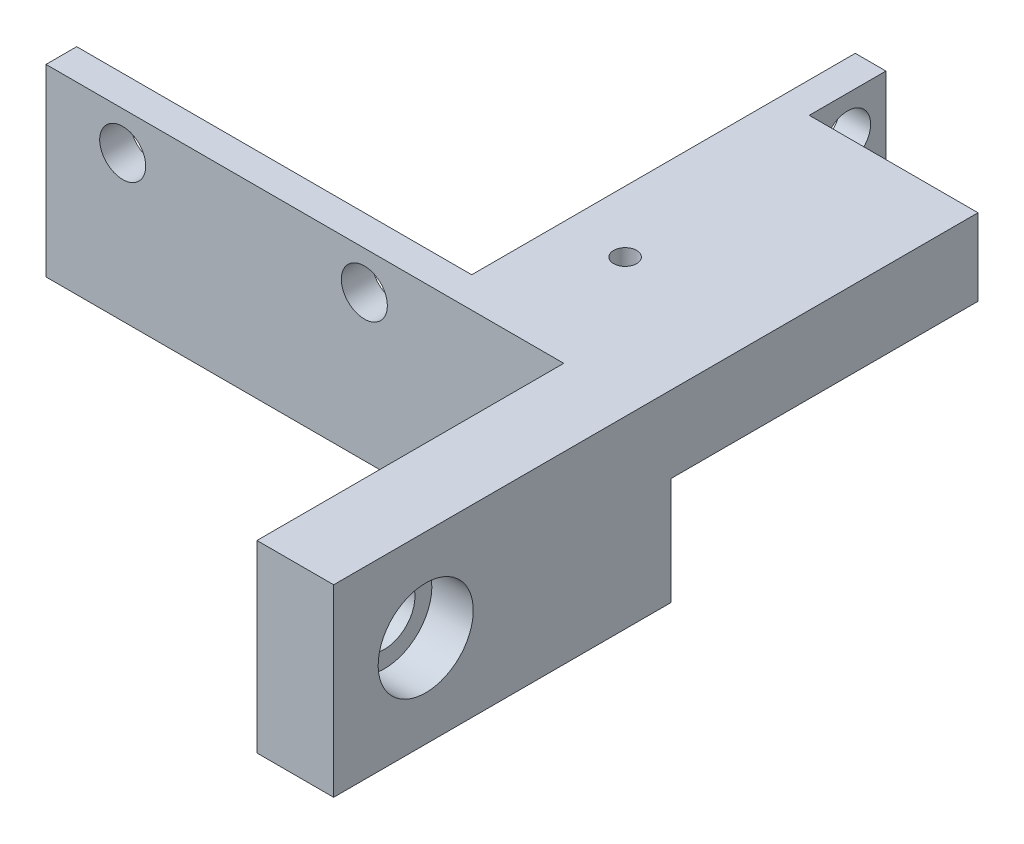
SolidWorks part; units mm, degrees
ref_plane "前视基准面" through (0, 0, 0) normal (0, 0, 1) x (1, 0, 0)
ref_plane "上视基准面" through (0, 0, 0) normal (0, 1, 0) x (1, 0, 0)
ref_plane "右视基准面" through (0, 0, 0) normal (1, 0, 0) x (0, 0, -1)
other "Configuration Table"
sketch "草图1" plane through (0, 0, 0) normal (0, 1, 0) x (1, 0, 0)
  line L1 (0, 0) -> (-25.75, 0)
  line L2 (0, 0) -> (0, 2)
  line L3 (0, 2) -> (-25.75, 2)
  line L4 (-25.75, 0) -> (-25.75, 2)
  dimension "D1" = 2
  dimension "D2" = 25.75
extrude "凸台-拉伸1" add sketch "草图1" along normal blind 5
sketch "草图2" plane through (0, 0, 0) normal (0, 0, -1) x (-1, 0, 0)
  line L0 (0, 0) -> (25.75, 0) construction
  line L1 (0, 5) -> (-13, 5)
  line L2 (0, 5) -> (0, 0)
  line L3 (0, 0) -> (-13, 0)
  line L4 (-13, 5) -> (-13, 0)
  line L6 (-13, 5) -> (-8, 5)
  line L7 (-13, 5) -> (-13, 0)
  line L8 (-13, 0) -> (-8, 0)
  line L9 (-8, 5) -> (-8, 0)
  dimension "D1" = 13
  dimension "D2" = 5
extrude "凸台-拉伸2" add sketch "草图2" along normal blind 22 contours L1 L4 L3 L2
extrude "凸台-拉伸3" add sketch "草图2<3>" against normal blind 20 contours L1 L9 L3 L4 region at (10.5, 2.5, 0)
sketch "草图2<3>" plane through (0, 0, 0) normal (0, 0, -1) x (-1, 0, 0) same geometry as "草图2"
sketch "草图3" plane through (0, 0, 0) normal (0, -1, 0) x (1, 0, 0)
  line L0 (13, -22) -> (13, 20) construction
  line L1 (-25.75, 0) -> (13, 0)
  line L2 (-25.75, 0) -> (-25.75, -2)
  line L3 (-25.75, -2) -> (13, -2)
  line L4 (13, 0) -> (13, -2)
  line L5 (0, -2) -> (-25.75, -2) construction
  line L7 (13, 0) -> (8, 0)
  line L8 (13, 0) -> (13, 20)
  line L9 (13, 20) -> (8, 20)
  line L10 (8, 0) -> (8, 20)
extrude "凸台-拉伸4" add sketch "草图3" along normal blind 7 contours L4 L3 L2 L1 | L7 L10 L9 L8
sketch "草图4" plane through (13, 0, 0) normal (1, 0, 0) x (0, 0, -1)
  line L0 (-20, 5) -> (-20, -7) construction
  circle A0 centre (-14, -1) radius 3.1
  circle A1 centre (-14, -1) radius 2
  point P5 (-20, -1)
  dimension "D2" = 6.2
  dimension "D3" = 4
  dimension "D1" = 6
extrude "切除-拉伸1" cut sketch "草图4" against normal through all contours A1
extrude "切除-拉伸2" cut sketch "草图4<3>" against normal blind 2.7 contours A0
sketch "草图4<3>" plane through (13, 0, 0) normal (1, 0, 0) x (0, 0, -1) same geometry as "草图4"
sketch "草图5" plane through (0, 0, 0) normal (-1, 0, 0) x (0, 0, 1)
  line L1 (-22, 5) -> (-27, 5)
  line L2 (-22, 5) -> (-22, 0)
  line L3 (-22, 0) -> (-27, 0)
  line L4 (-27, 5) -> (-27, 0)
  circle A0 centre (-24.5, 2.5) radius 1.5
  point P7 (0, 0)
  point P8 (-27, 2.5)
  point P9 (-25, 0.9)
  point P11 (0, 0)
  dimension "D3" = 3
  dimension "D1" = 5
  dimension "D2" = 2.5
extrude "凸台-拉伸5" add sketch "草图5" against normal blind 2
sketch "草图6" plane through (0, 0, 0) normal (0, 0, 1) x (1, 0, 0)
  line L0 (8, 5) -> (-25.75, 5) construction
  line L1 (-25.75, 5) -> (-25.75, -7) construction
  circle A0 centre (-20.75, 2.5) radius 1.5
  circle A1 centre (-5, 2.5) radius 1.5
  point P4 (0, 0)
  dimension "D2" = 3
  dimension "D1" = 2.5
  dimension "D3" = 15.75
  dimension "D4" = 5
extrude "切除-拉伸3" cut sketch "草图6" against normal through all contours A0 | A1
sketch "草图7" plane through (0, 5, 0) normal (0, 1, 0) x (1, 0, 0)
  line L0 (0, 27) -> (0, 2) construction
  line L1 (0, 2) -> (-25.75, 2) construction
  circle A0 centre (4, 8) radius 0.75
  dimension "D1" = 1.5
  dimension "D2" = 4
  dimension "D3" = 6
extrude "切除-拉伸4" cut sketch "草图7" against normal through all contours A0
